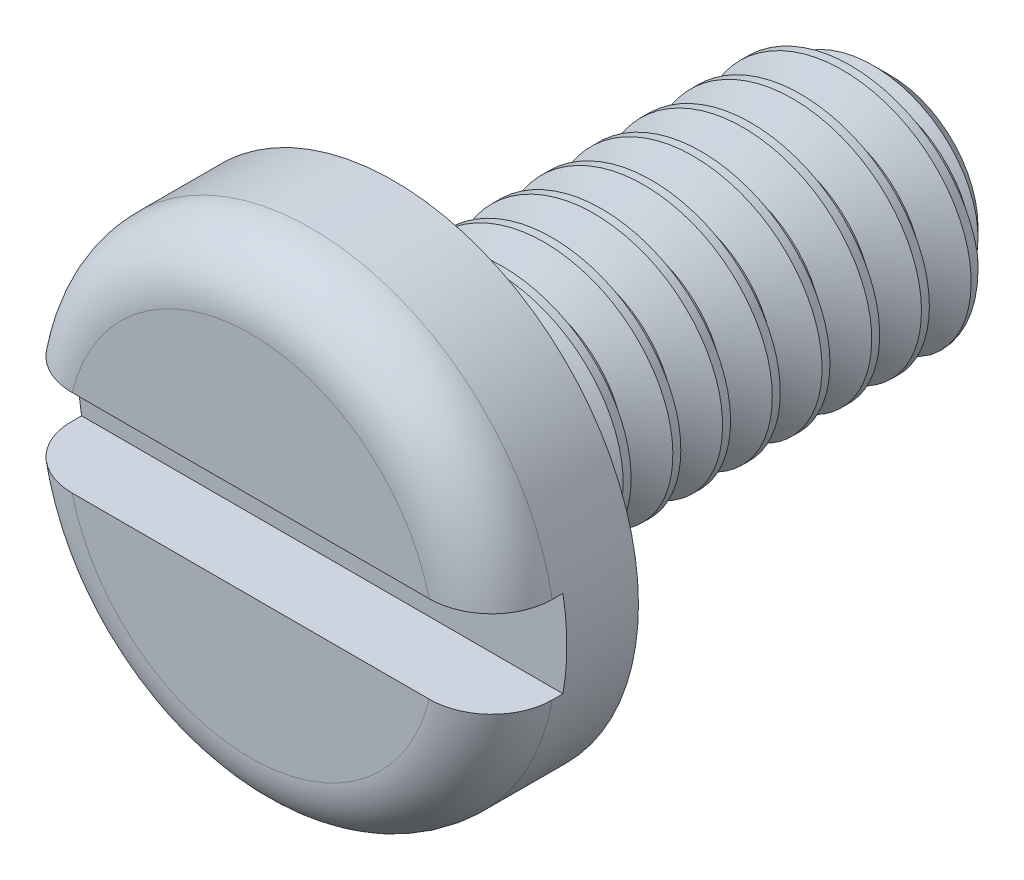
SolidWorks part; units mm, degrees
ref_plane "Front" through (0, 0, 0) normal (0, 0, 1) x (1, 0, 0)
ref_plane "Top" through (0, 0, 0) normal (0, 1, 0) x (1, 0, 0)
ref_plane "Right" through (0, 0, 0) normal (1, 0, 0) x (0, 0, -1)
sketch "Sketch1" plane through (0, 0, 0) normal (0, 0, 1) x (1, 0, 0)
  circle A0 centre (0, 0) radius 6.2484
  dimension "Head Dia" = 12.4968
extrude "Extrude3" add sketch "Sketch1" along normal blind 3.6576
sketch "Sketch11" plane through (0, 0, 0) normal (1, 0, 0) x (0, 0, -1)
  line L0 (0, 0) -> (-3.9116, 0) construction
  line L1 (-3.6576, 4.6939) -> (-3.6576, 0)
  line L4 (-3.6576, 6.2484) -> (-3.6576, -6.2484) construction
  line L5 (-3.9116, 6.4983) -> (0, 6.4983)
  line L7 (0, 6.4983) -> (0, 6.2484)
  line L8 (-2.1031, 6.2484) -> (0, 6.2484)
  line L9 (0, -6.2484) -> (0, 6.2484) construction
  line L11 (0, 6.2484) -> (-3.6576, 6.2484) construction
  line L13 (-3.6576, 0) -> (-3.9116, 0)
  line L14 (-3.9116, 0) -> (-3.9116, 6.4983)
  arc A2 (-3.6576, 4.6939) -> (-2.1031, 6.2484) centre (-2.1031, 4.6939) cw
  dimension "D4" = 1.5545
  dimension "D3" = 0.254
  dimension "D5" = 0.2499
revolve "Cut-Revolve3" cut sketch "Sketch11" angle 360 about L0
sketch "Sketch4" plane through (0, 0, 0) normal (1, 0, 0) x (0, 0, -1)
  line L0 (0, 0) -> (12.7, 0)
  line L3 (12.7, 0) -> (12.7, 3.175)
  line L4 (12.7, 3.175) -> (0, 3.175)
  line L6 (0, 3.175) -> (0, 0)
  line L9 (12.7, 3.175) -> (12.7, -3.175) construction
  dimension "length" = 12.7
  dimension "dia" = 6.35
revolve "Revolve1" add sketch "Sketch4" angle 360 about L0
sketch "Sketch13" plane through (0, 0, -12.7) normal (0, 0, -1) x (-1, 0, 0)
  circle A2 centre (0, 0) radius 3.175
curve "Helix/Spiral1" pitch 1.27 height 16.3576 radius 3.175 centre (0, 0, -12.7) axis (0, 0, 1) start towards (1, 0, 0)
chamfer "Chamfer2" distance 0.9525 angle 45 1 edges at (3.175, 0, -12.7)
sketch "Sketch14" plane through (0, 0, 0) normal (1, 0, 0) x (0, 0, -1)
  line L0 (12.7, 3.2147) -> (13.8113, 3.2147)
  line L1 (13.8113, 3.2147) -> (13.335, 2.3555)
  line L2 (13.335, 2.3555) -> (13.1763, 2.3555)
  line L3 (13.1763, 2.3555) -> (12.7, 3.2147)
  line L4 (12.9381, 2.7851) -> (13.5731, 2.7851) construction
  dimension "D1" = 0.1588
  dimension "D2" = 58
  dimension "D3" = 0.635
  dimension "D4" = 0.0397
sweep "Cut-Sweep1" cut profiles "Sketch14" path "Helix/Spiral1" align with end faces yes
ref_plane "Plane1" through (0, 0, 25.4) normal (0, 0, -1) x (-1, 0, 0)
sketch "Sketch29" [suppressed] plane through (0, 0, 28.575) normal (0, 0, -1) x (-1, 0, 0)
  circle A0 centre (0, 0) radius 1.7526 construction
  circle A1 centre (0, 0) radius 1.7526
  point P3 (0, -1.7526)
  point P4 (0, 1.7526)
extrude "Extrude11" [suppressed] add sketch "Sketch29" against normal up to surface (28.575 mm away) up to plane "Front"
sketch "Sketch26" plane through (0, 0, 0) normal (0, 0, 1) x (1, 0, 0)
  circle A1 centre (0, 0) radius 0.5461
  dimension "D1" = 1.0922
extrude "Extrude13" add sketch "Sketch26" along normal up to surface (3.6576 mm away) up to face at (0, 4.6939, 3.6576)
sketch "Sketch31" plane through (0, 0, 3.6576) normal (0, 0, 1) x (1, 0, 0)
  line L0 (-6.2484, 1.1112) -> (6.2484, -1.1112) construction
  line L1 (-6.2484, 1.1112) -> (6.2484, 1.1113)
  line L2 (-6.2484, 1.1112) -> (-6.2484, -1.1113)
  line L3 (-6.2484, -1.1113) -> (6.2484, -1.1112)
  line L4 (6.2484, 1.1113) -> (6.2484, -1.1112)
  circle A0 centre (0, 0) radius 6.2484 construction
  dimension "D1" = 2.2225
extrude "Extrude15" cut sketch "Sketch31" against normal blind 1.8288
sketch "Sketch18" plane through (0, 0, 0) normal (1, 0, 0) x (0, 0, -1)
  line L1 (12.7, 3.175) -> (0, 3.175) construction
  point P0 (10.795, -3.175)
  point P1 (11.43, 3.175)
  point P2 (-3.6576, 4.6939)
  dimension "D1" = 1.27
  dimension "D2" = 1.905
equation "\"D3@Helix/Spiral1\" = \"length@Sketch4\" + \"Head Ht@Extrude3\""
equation "\"D1@Sketch14\" = \"D4@Helix/Spiral1\" * .125"
equation "\"D3@Sketch14\" = \"D4@Helix/Spiral1\" * .5"
equation "\"D5@Sketch11\" = \"Head Dia@Sketch1\" * .02"
equation "\"D4@Sketch14\" = \"D1@Sketch14\" * .25"
equation "\"D1@Chamfer2\" = \"D4@Helix/Spiral1\" * .75"
equation "\"D1@Sketch18\" = \"D4@Helix/Spiral1\""
equation "\"D2@Sketch18\" = \"D4@Helix/Spiral1\" * 1.5"
equation "\"D1@Extrude15\" = \"Head Ht@Extrude3\" * .5"
equation "\"D4@Sketch11\" = \"Head Ht@Extrude3\" * .425"
equation "\"D1@Sketch31\" = \"D4@Helix/Spiral1\" * 1.75"
